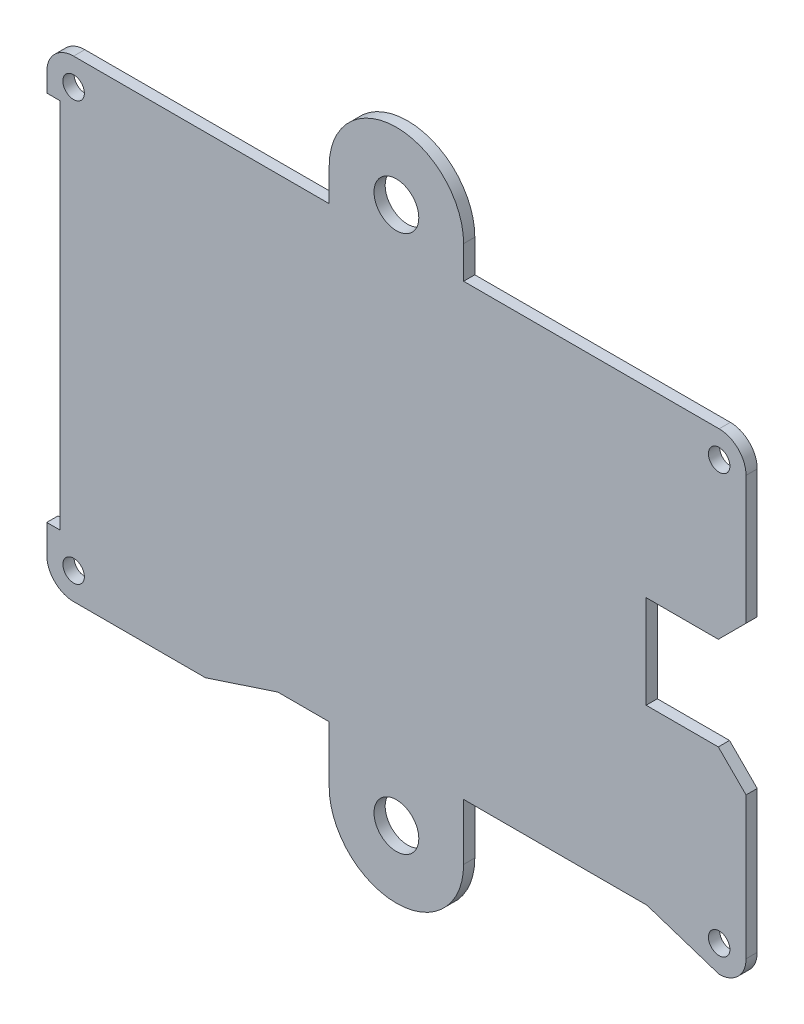
SolidWorks part; units mm, degrees
ref_plane "Front Plane" through (0, 0, 0) normal (0, 0, 1) x (1, 0, 0)
ref_plane "Top Plane" through (0, 0, 0) normal (0, 1, 0) x (1, 0, 0)
ref_plane "Right Plane" through (0, 0, 0) normal (1, 0, 0) x (0, 0, -1)
sketch "Sketch1" plane through (0, 0, 0) normal (0, 0, 1) x (1, 0, 0)
  line L0 (-301.9473, 111.7465) -> (-305.8779, 115.6771) construction
  line L1 (-305.8779, 115.6771) -> (-316.1078, 115.6771) construction
  line L2 (-316.1078, 115.6771) -> (-316.1078, 128.8851) construction
  line L3 (-316.1078, 128.8851) -> (-305.8779, 128.8851) construction
  line L4 (-305.8779, 128.8851) -> (-301.9473, 132.8157) construction
  line L5 (-301.9473, 132.8157) -> (-301.9473, 150.9704) construction
  line L6 (-305.7573, 154.7804) -> (-397.2471, 154.7804) construction
  line L7 (-401.0571, 150.9566) -> (-401.0571, 148.341) construction
  line L8 (-401.0571, 148.341) -> (-399.1521, 148.341) construction
  line L9 (-399.1521, 148.341) -> (-399.1521, 95.6449) construction
  line L10 (-399.1521, 95.6449) -> (-401.0571, 95.6449) construction
  line L11 (-401.0571, 95.6449) -> (-401.0571, 91.6593) construction
  line L12 (-397.2472, 87.8217) -> (-378.5565, 87.8217) construction
  line L13 (-378.5565, 87.8217) -> (-368.3165, 91.1883) construction
  line L14 (-368.3165, 91.1883) -> (-315.9973, 91.1883) construction
  line L15 (-315.9973, 91.1883) -> (-305.7573, 87.8217) construction
  line L16 (-301.9473, 91.6317) -> (-301.9473, 111.7465) construction
  line L17 (-301.9473, 111.7465) -> (-305.8779, 115.6771)
  line L18 (-305.8779, 115.6771) -> (-316.1078, 115.6771)
  line L19 (-316.1078, 115.6771) -> (-316.1078, 128.8851)
  line L20 (-316.1078, 128.8851) -> (-305.8779, 128.8851)
  line L21 (-305.8779, 128.8851) -> (-301.9473, 132.8157)
  line L22 (-301.9473, 132.8157) -> (-301.9473, 150.9704)
  line L23 (-305.7573, 154.7804) -> (-397.2471, 154.7804)
  line L24 (-401.0571, 150.9566) -> (-401.0571, 148.341)
  line L25 (-401.0571, 148.341) -> (-399.1521, 148.341)
  line L26 (-399.1521, 148.341) -> (-399.1521, 95.6449)
  line L27 (-399.1521, 95.6449) -> (-401.0571, 95.6449)
  line L28 (-401.0571, 95.6449) -> (-401.0571, 91.6593)
  line L29 (-397.2472, 87.8217) -> (-378.5565, 87.8217)
  line L30 (-378.5565, 87.8217) -> (-368.3165, 91.1883)
  line L31 (-368.3165, 91.1883) -> (-315.9973, 91.1883)
  line L32 (-315.9973, 91.1883) -> (-305.7573, 87.8217)
  line L33 (-301.9473, 91.6317) -> (-301.9473, 111.7465)
  circle A0 centre (-305.7573, 91.6317) radius 1.3559 construction
  circle A1 centre (-305.7573, 150.9704) radius 1.3559 construction
  circle A2 centre (-397.2471, 150.9704) radius 1.3559 construction
  circle A3 centre (-397.2472, 91.6317) radius 1.3559 construction
  circle A4 centre (-305.7573, 91.6317) radius 1.3559
  circle A5 centre (-305.7573, 150.9704) radius 1.3559
  circle A6 centre (-397.2471, 150.9704) radius 1.3559
  circle A7 centre (-397.2472, 91.6317) radius 1.3559
  arc A8 (-301.9473, 150.9704) -> (-305.7573, 154.7804) centre (-305.7573, 150.9704) ccw construction
  arc A9 (-397.2471, 154.7804) -> (-401.0571, 150.9566) centre (-397.2471, 150.9704) ccw construction
  arc A10 (-401.0571, 91.6593) -> (-397.2472, 87.8217) centre (-397.2472, 91.6317) ccw construction
  arc A11 (-305.7573, 87.8217) -> (-301.9473, 91.6317) centre (-305.7573, 91.6317) ccw construction
  arc A12 (-301.9473, 150.9704) -> (-305.7573, 154.7804) centre (-305.7573, 150.9704) ccw
  arc A13 (-397.2471, 154.7804) -> (-401.0571, 150.9566) centre (-397.2471, 150.9704) ccw
  arc A14 (-401.0571, 91.6593) -> (-397.2472, 87.8217) centre (-397.2472, 91.6317) ccw
  arc A15 (-305.7573, 87.8217) -> (-301.9473, 91.6317) centre (-305.7573, 91.6317) ccw
extrude "Boss-Extrude1" add sketch "Sketch1" along normal blind 1.5875
sketch "Sketch2" plane through (0, 0, 1.5875) normal (0, 0, 1) x (1, 0, 0)
  line L0 (-351.5022, 121.301) -> (-351.5022, 159.401) construction
  line L1 (-301.9473, 150.9704) -> (-301.9473, 91.6317) construction
  line L2 (-401.0571, 121.301) -> (-301.9473, 121.301) construction
  line L3 (-351.5022, 83.201) -> (-351.5022, 159.401) construction
  line L4 (-361.0272, 83.201) -> (-361.0272, 159.401)
  line L5 (-341.9772, 83.201) -> (-341.9772, 159.401)
  line L6 (-361.0272, 154.7804) -> (-341.9772, 154.7804)
  line L7 (-305.7573, 154.7804) -> (-397.2471, 154.7804) construction
  line L8 (-361.0272, 91.6317) -> (-341.9772, 91.6317)
  circle A0 centre (-351.5022, 159.401) radius 3.175
  arc A1 (-361.0272, 83.201) -> (-341.9772, 83.201) centre (-351.5022, 83.201) ccw
  arc A2 (-341.9772, 159.401) -> (-361.0272, 159.401) centre (-351.5022, 159.401) ccw
  circle A3 centre (-351.5022, 83.201) radius 3.175
  point P13 (-351.5022, 121.301)
  line M11 (-305.7573, 154.7804) -> (-397.2471, 154.7804)
  line M21 (-368.3165, 91.1883) -> (-315.9973, 91.1883)
  dimension "D1" = 6.35
  dimension "D2" = 38.1
  dimension "D3" = 19.05
extrude "Boss-Extrude2" add sketch "Sketch2" against normal blind 1.5875 contours L5 A2 L4 A0 M11 | L4 A1 L5 A3 M21 region at (-360.7899, 157.0907, 1.5875) region at (-351.5022, 90.9295, 1.5875)
sketch "Sketch3" plane through (0, 0, 1.5875) normal (0, 0, 1) x (1, 0, 0)
  circle A0 centre (-397.2471, 150.9704) radius 1.524
  circle A1 centre (-305.7573, 150.9704) radius 1.524
  circle A2 centre (-305.7573, 91.6317) radius 1.524
  circle A3 centre (-397.2472, 91.6317) radius 1.524
  dimension "D1" = 3.048
extrude "Cut-Extrude1" cut sketch "Sketch3" against normal through all
